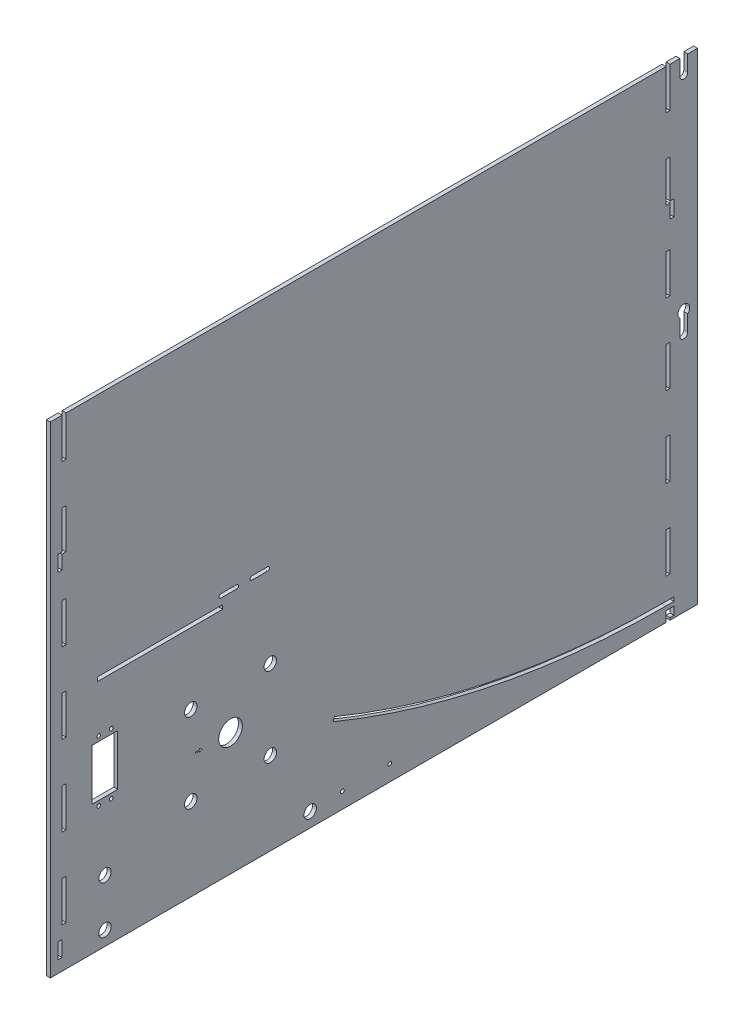
SolidWorks part; units mm, degrees
ref_plane "Front Plane" through (0, 0, 0) normal (0, 0, 1) x (1, 0, 0)
ref_plane "Top Plane" through (0, 0, 0) normal (0, 1, 0) x (1, 0, 0)
ref_plane "Right Plane" through (0, 0, 0) normal (1, 0, 0) x (0, 0, -1)
sketch "Sketch1" plane through (0, 0, 0) normal (1, 0, 0) x (0, 0, -1)
  line L0 (-141.0275, 130.552) -> (-77.0275, 130.552) construction
  line L1 (-244.475, 387.35) -> (244.475, 387.35)
  line L2 (-244.475, 387.35) -> (-244.475, 0)
  line L3 (-244.475, 0) -> (244.475, 0)
  line L4 (244.475, 387.35) -> (244.475, 0)
  line L5 (-77.0275, 130.552) -> (-77.0275, 66.552) construction
  line L6 (-77.0275, 66.552) -> (-141.0275, 66.552) construction
  line L7 (-141.0275, 66.552) -> (-141.0275, 130.552) construction
  line L8 (-215.1157, 149.1948) -> (-204.9557, 149.1948) construction
  line L9 (-220.2857, 145.2948) -> (-199.7857, 145.2948)
  line L10 (-220.2857, 145.2948) -> (-220.2857, 104.2948)
  line L11 (-220.2857, 104.2948) -> (-199.7857, 104.2948)
  line L12 (-199.7857, 145.2948) -> (-199.7857, 104.2948)
  line L15 (-204.9557, 100.3948) -> (-215.1157, 100.3948) construction
  line L18 (-210.0357, 100.3948) -> (-210.0357, 149.1948) construction
  line L19 (-220.2857, 124.7948) -> (-199.7857, 124.7948) construction
  line L20 (-241.3, 387.35) -> (-241.3, 0) construction
  line L21 (241.3, 387.35) -> (241.3, 0) construction
  line L22 (-244.475, 193.675) -> (-241.3, 193.675) construction
  line L23 (244.475, 193.675) -> (241.3, 193.675) construction
  line L24 (-244.475, 6.35) -> (244.475, 6.35) construction
  line L25 (-241.3, 190.754) -> (-215.9, 190.754) construction
  line L26 (-115.3775, 190.754) -> (-109.0275, 190.754) construction
  line L27 (-215.9, 190.754) -> (-115.3775, 190.754)
  line L28 (-215.9, 190.754) -> (-215.9, 187.579)
  line L29 (-215.9, 187.579) -> (-115.3775, 187.579)
  line L30 (-115.3775, 190.754) -> (-115.3775, 187.579)
  line L31 (-109.0275, 190.754) -> (-109.0275, 187.579) construction
  line L32 (-109.0275, 187.579) -> (-115.3775, 187.579) construction
  line L33 (-215.9, 187.579) -> (-241.3, 187.579) construction
  line L34 (-26.6311, 64.8518) -> (-25.4161, 67.7851)
  line L35 (241.3, 11.557) -> (241.3, 14.732)
  line L36 (-26.0236, 66.3185) -> (-68.1062, 83.7497) construction
  line L37 (241.3, 13.1445) -> (249.9158, 13.1445) construction
  line L38 (-26.0236, 66.3185) -> (-57.3534, 66.3185) construction
  line L39 (-91.8775, 197.579) -> (-116.8775, 197.579) construction
  line L40 (-244.475, 387.35) -> (-254, 387.35)
  line L41 (-244.475, 387.35) -> (-244.475, 0)
  line L42 (-244.475, 0) -> (-254, 0)
  line L43 (-254, 387.35) -> (-254, 0)
  line L44 (244.475, 387.35) -> (266.7, 387.35)
  line L45 (244.475, 387.35) -> (244.475, 0)
  line L46 (244.475, 0) -> (266.7, 0)
  line L47 (266.7, 387.35) -> (266.7, 0)
  line L48 (-116.8775, 199.079) -> (-104.1775, 199.079)
  line L49 (-104.1775, 196.079) -> (-116.8775, 196.079)
  line L50 (-91.8775, 196.079) -> (-79.1775, 196.079)
  line L51 (-79.1775, 199.079) -> (-91.8775, 199.079)
  circle A0 centre (-109.0275, 98.552) radius 89.027 construction
  circle A1 centre (-109.0275, 98.552) radius 9.525
  circle A2 centre (-141.0275, 130.552) radius 5
  circle A3 centre (-77.0275, 130.552) radius 5
  circle A4 centre (-141.0275, 66.552) radius 5
  circle A5 centre (-77.0275, 66.552) radius 5
  circle A10 centre (-215.1157, 149.1948) radius 1.5
  circle A11 centre (-204.9557, 149.1948) radius 1.5
  circle A12 centre (-215.1157, 100.3948) radius 1.5
  circle A13 centre (-204.9557, 100.3948) radius 1.5
  arc A14 (241.3, 11.557) -> (-26.6311, 64.8518) centre (241.3, 711.6946) cw
  arc A15 (241.3, 14.732) -> (-25.4161, 67.7851) centre (241.3, 711.6946) cw
  arc A16 (241.3, 13.1445) -> (-26.0236, 66.3185) centre (241.3, 711.6946) cw construction
  circle A17 centre (-116.8775, 197.579) radius 1.5
  circle A18 centre (-91.8775, 197.579) radius 1.5
  arc A19 (-104.1775, 199.079) -> (-104.1775, 196.079) centre (-104.1775, 197.579) cw
  arc A20 (-79.1775, 196.079) -> (-79.1775, 199.079) centre (-79.1775, 197.579) ccw
  point P16 (-109.0275, 130.552)
  point P18 (-141.0275, 98.552)
  point P31 (-210.0357, 104.2948)
  point P34 (-210.0357, 124.7948)
  point P38 (-198.0545, 98.552)
  point P57 (0, 0)
  point P60 (-109.0275, 9.525)
  dimension "D3" = 178.054
  dimension "D5" = 10
  dimension "D6" = 19.05
  dimension "D8" = 3
  dimension "D28" = 3
  dimension "D4" = 64
  dimension "D7" = 10.16
  dimension "D9" = 20.5
  dimension "D10" = 41
  dimension "D11" = 48.8
  dimension "D12" = 11.9812
  dimension "D13" = 26.2428
  dimension "D14" = 3.175
  dimension "D15" = 482.6
  dimension "D16" = 6.35
  dimension "D2" = 381
  dimension "D17" = 25.4
  dimension "D18" = 3.175
  dimension "D19" = 6.35
  dimension "D20" = 100.5225
  dimension "D21" = 9.525
  dimension "D23" = 3.175
  dimension "D24" = 13.1445
  dimension "D25" = 22.5
  dimension "D26" = 9.525
  dimension "D27" = 22.225
  dimension "D29" = 6.825
  dimension "D30" = 25
  dimension "D31" = 12.7
  dimension "D32" = 1.5
  dimension "D22" = 274.32
extrude "Boss-Extrude1" add sketch "Sketch1" along normal blind 3.175 contours L4 L1 L2 L3 A15 L35 A14 L34 A13 A12 A11 A10 A5 A4 A3 A2 A1 L9 L12 L11 L10 L27 L30 L29 L28 | L47 L44 L4 L46 | L40 L43 L42 L2 region at (0, 195.0661, -1.1642) region at (0, 193.675, 249.2375) region at (0, 193.675, -255.5875)
sketch "Sketch2" plane through (0, 0, 0) normal (-1, 0, 0) x (0, 0, 1)
  line L34 (-241.3, 387.35) -> (-241.3, 0) construction
  line L35 (-244.475, 387.35) -> (-241.3, 387.35)
  line L36 (-244.475, 387.35) -> (-244.475, 355.0708)
  line L37 (-244.475, 355.0708) -> (-241.3, 355.0708)
  line L38 (-241.3, 387.35) -> (-241.3, 355.0708)
  line L39 (241.3, 387.35) -> (241.3, 0) construction
  line L40 (244.475, 387.35) -> (241.3, 387.35)
  line L41 (244.475, 387.35) -> (244.475, 355.0708)
  line L42 (244.475, 355.0708) -> (241.3, 355.0708)
  line L43 (241.3, 387.35) -> (241.3, 355.0708)
  line L44 (-244.475, 355.0708) -> (-244.475, 322.7917)
  line L45 (-244.475, 355.0708) -> (-241.3, 355.0708)
  line L46 (-241.3, 355.0708) -> (-241.3, 322.7917)
  line L47 (-244.475, 322.7917) -> (-241.3, 322.7917)
  line L48 (244.475, 355.0708) -> (244.475, 322.7917)
  line L49 (244.475, 355.0708) -> (241.3, 355.0708)
  line L50 (241.3, 355.0708) -> (241.3, 322.7917)
  line L51 (244.475, 322.7917) -> (241.3, 322.7917)
  line L52 (-244.475, 322.7917) -> (-244.475, 290.5125)
  line L53 (-244.475, 322.7917) -> (-241.3, 322.7917)
  line L54 (-241.3, 322.7917) -> (-241.3, 290.5125)
  line L55 (-244.475, 290.5125) -> (-241.3, 290.5125)
  line L56 (244.475, 322.7917) -> (244.475, 290.5125)
  line L57 (244.475, 322.7917) -> (241.3, 322.7917)
  line L58 (241.3, 322.7917) -> (241.3, 290.5125)
  line L59 (244.475, 290.5125) -> (241.3, 290.5125)
  line L60 (-244.475, 290.5125) -> (-244.475, 258.2333)
  line L61 (-244.475, 290.5125) -> (-241.3, 290.5125)
  line L62 (-241.3, 290.5125) -> (-241.3, 258.2333)
  line L63 (-244.475, 258.2333) -> (-241.3, 258.2333)
  line L64 (244.475, 290.5125) -> (244.475, 258.2333)
  line L65 (244.475, 290.5125) -> (241.3, 290.5125)
  line L66 (241.3, 290.5125) -> (241.3, 258.2333)
  line L67 (244.475, 258.2333) -> (241.3, 258.2333)
  line L68 (-244.475, 258.2333) -> (-244.475, 225.9542)
  line L69 (-244.475, 258.2333) -> (-241.3, 258.2333)
  line L70 (-241.3, 258.2333) -> (-241.3, 225.9542)
  line L71 (-244.475, 225.9542) -> (-241.3, 225.9542)
  line L72 (244.475, 258.2333) -> (244.475, 225.9542)
  line L73 (244.475, 258.2333) -> (241.3, 258.2333)
  line L74 (241.3, 258.2333) -> (241.3, 225.9542)
  line L75 (244.475, 225.9542) -> (241.3, 225.9542)
  line L76 (-244.475, 225.9542) -> (-244.475, 193.675)
  line L77 (-244.475, 225.9542) -> (-241.3, 225.9542)
  line L78 (-241.3, 225.9542) -> (-241.3, 193.675)
  line L79 (-244.475, 193.675) -> (-241.3, 193.675)
  line L80 (244.475, 225.9542) -> (244.475, 193.675)
  line L81 (244.475, 225.9542) -> (241.3, 225.9542)
  line L82 (241.3, 225.9542) -> (241.3, 193.675)
  line L83 (244.475, 193.675) -> (241.3, 193.675)
  line L84 (-244.475, 193.675) -> (-244.475, 161.3958)
  line L85 (-244.475, 193.675) -> (-241.3, 193.675)
  line L86 (-241.3, 193.675) -> (-241.3, 161.3958)
  line L87 (-244.475, 161.3958) -> (-241.3, 161.3958)
  line L88 (244.475, 193.675) -> (244.475, 161.3958)
  line L89 (244.475, 193.675) -> (241.3, 193.675)
  line L90 (241.3, 193.675) -> (241.3, 161.3958)
  line L91 (244.475, 161.3958) -> (241.3, 161.3958)
  line L92 (-244.475, 161.3958) -> (-244.475, 129.1167)
  line L93 (-244.475, 161.3958) -> (-241.3, 161.3958)
  line L94 (-241.3, 161.3958) -> (-241.3, 129.1167)
  line L95 (-244.475, 129.1167) -> (-241.3, 129.1167)
  line L96 (244.475, 161.3958) -> (244.475, 129.1167)
  line L97 (244.475, 161.3958) -> (241.3, 161.3958)
  line L98 (241.3, 161.3958) -> (241.3, 129.1167)
  line L99 (244.475, 129.1167) -> (241.3, 129.1167)
  line L100 (-244.475, 129.1167) -> (-244.475, 96.8375)
  line L101 (-244.475, 129.1167) -> (-241.3, 129.1167)
  line L102 (-241.3, 129.1167) -> (-241.3, 96.8375)
  line L103 (-244.475, 96.8375) -> (-241.3, 96.8375)
  line L104 (244.475, 129.1167) -> (244.475, 96.8375)
  line L105 (244.475, 129.1167) -> (241.3, 129.1167)
  line L106 (241.3, 129.1167) -> (241.3, 96.8375)
  line L107 (244.475, 96.8375) -> (241.3, 96.8375)
  line L108 (0, 387.35) -> (0, 0) construction
  line L109 (244.475, 387.35) -> (-244.475, 387.35) construction
  line L110 (-244.475, 96.8375) -> (-244.475, 64.5583)
  line L111 (-244.475, 96.8375) -> (-241.3, 96.8375)
  line L112 (-241.3, 96.8375) -> (-241.3, 64.5583)
  line L113 (-244.475, 64.5583) -> (-241.3, 64.5583)
  line L114 (244.475, 96.8375) -> (244.475, 64.5583)
  line L115 (244.475, 96.8375) -> (241.3, 96.8375)
  line L116 (241.3, 96.8375) -> (241.3, 64.5583)
  line L117 (244.475, 64.5583) -> (241.3, 64.5583)
  line L118 (-244.475, 64.5583) -> (-244.475, 32.2792)
  line L119 (-244.475, 64.5583) -> (-241.3, 64.5583)
  line L120 (-241.3, 64.5583) -> (-241.3, 32.2792)
  line L121 (-244.475, 32.2792) -> (-241.3, 32.2792)
  line L122 (244.475, 64.5583) -> (244.475, 32.2792)
  line L123 (244.475, 64.5583) -> (241.3, 64.5583)
  line L124 (241.3, 64.5583) -> (241.3, 32.2792)
  line L125 (244.475, 32.2792) -> (241.3, 32.2792)
  line L126 (-244.475, 32.2792) -> (-244.475, 0)
  line L127 (-244.475, 32.2792) -> (-241.3, 32.2792)
  line L128 (-241.3, 32.2792) -> (-241.3, 0)
  line L129 (-244.475, 0) -> (-241.3, 0)
  line L130 (244.475, 32.2792) -> (244.475, 0)
  line L131 (244.475, 32.2792) -> (241.3, 32.2792)
  line L132 (241.3, 32.2792) -> (241.3, 0)
  line L133 (244.475, 0) -> (241.3, 0)
  line M136 (254, 387.35) -> (-266.7, 387.35)
  dimension "D2" = 387.35
  dimension "D3" = 32.2792
  dimension "D1" = 12
extrude "Cut-Extrude1" cut sketch "Sketch2" against normal through all contours L118 L121 L120 L113 | L100 L103 L102 L95 | L84 L87 L86 L79 | L52 L55 L54 L47 | L38 L36 L37 M136 | L68 L71 L70 L63 | L43 L42 L41 M136 | L59 L56 L51 L58 | L75 L72 L67 L74 | L91 L88 L83 L90 | L107 L104 L99 L106 | L125 L122 L117 L124 region at (0, 371.2104, 242.8875) region at (0, 371.2104, -242.8875) region at (0, 306.6521, -242.8875) region at (0, 306.6521, 242.8875) region at (0, 242.0938, -242.8875) region at (0, 242.0938, 242.8875) region at (0, 177.5354, -242.8875) region at (0, 177.5354, 242.8875) region at (0, 112.9771, -242.8875) region at (0, 112.9771, 242.8875) region at (0, 48.4188, -242.8875) region at (0, 48.4188, 242.8875)
sketch "Sketch3" plane through (0, 0, 0) normal (-1, 0, 0) x (0, 0, 1)
  line L0 (-258.7625, 206.375) -> (-258.7625, 193.675)
  line L1 (-252.4125, 193.675) -> (-252.4125, 206.375)
  line L2 (-258.7625, 387.35) -> (-258.7625, 374.65)
  line L3 (-244.475, 387.35) -> (-266.7, 387.35) construction
  line L4 (-252.4125, 374.65) -> (-252.4125, 387.35)
  line L5 (-258.7625, 387.35) -> (-252.4125, 387.35)
  line L6 (-255.5875, 374.65) -> (-255.5875, 193.675) construction
  line L7 (-266.7, 387.35) -> (-266.7, 0) construction
  line L9 (-241.3, 11.557) -> (-247.65, 11.557)
  line L10 (-241.3, 11.557) -> (-241.3, 14.732)
  line L11 (-241.3, 14.732) -> (-247.65, 14.732)
  line L12 (-247.65, 11.557) -> (-247.65, 14.732)
  circle A0 centre (-255.5875, 209.9248) radius 4.7625
  arc A1 (-258.7625, 193.675) -> (-252.4125, 193.675) centre (-255.5875, 193.675) ccw
  arc A2 (-258.7625, 374.65) -> (-252.4125, 374.65) centre (-255.5875, 374.65) ccw
  point P16 (-255.5875, 387.35)
  point P17 (-255.5875, 387.35)
  point P24 (-266.7, 193.675)
  dimension "D1" = 3.175
  dimension "D2" = 9.525
  dimension "D3" = 12.7
  dimension "D4" = 6.35
extrude "Cut-Extrude2" cut sketch "Sketch3" against normal through all contours L12 L9 L10 L11 | A0 L6 | L0 A1 L1 A0 | L6 A0 | L2 A2 L4 L5 region at (0, 205.316, -257.3479) region at (0, 379.7367, -255.5875) region at (0, 209.9248, -257.6088) region at (0, 209.9248, -253.5662) region at (0, 13.1445, -244.475)
sketch "Sketch4" plane through (0, 0, 0) normal (-1, 0, 0) x (0, 0, 1)
  line L0 (210.0357, 49.5948) -> (210.0357, 11.4948) construction
  line L1 (210.0357, 11.4948) -> (44.9357, 11.4948) construction
  line L2 (210.0357, 49.5948) -> (210.0357, 100.3948) construction
  circle A0 centre (210.0357, 49.5948) radius 5
  circle A1 centre (44.9357, 11.4948) radius 5
  circle A2 centre (210.0357, 11.4948) radius 5
  dimension "D1" = 10
  dimension "D2" = 50.8
  dimension "D3" = 38.1
  dimension "D4" = 165.1
extrude "Cut-Extrude3" cut sketch "Sketch4" against normal through all
sketch "Sketch5" plane through (0, 0, 0) normal (-1, 0, 0) x (0, 0, 1)
  line L0 (244.475, 0) -> (-244.475, 0) construction
  line L1 (-19.05, 12.7) -> (19.05, 12.7) construction
  circle A0 centre (-19.05, 12.7) radius 1.5
  circle A1 centre (19.05, 12.7) radius 1.5
  point P6 (0, 12.7)
  dimension "D3" = 3
  dimension "D1" = 38.1
  dimension "D2" = 12.7
extrude "Cut-Extrude4" cut sketch "Sketch5" against normal through all
sketch "Sketch6" plane through (0, 0, 0) normal (-1, 0, 0) x (0, 0, 1)
  line L0 (244.475, 387.35) -> (244.475, 355.0708) construction
  line L1 (244.475, 292.1) -> (247.65, 292.1)
  line L2 (244.475, 292.1) -> (244.475, 279.4)
  line L3 (244.475, 279.4) -> (247.65, 279.4)
  line L4 (247.65, 292.1) -> (247.65, 279.4)
  line L6 (244.475, 64.5583) -> (244.475, 32.2792) construction
  line L7 (244.475, 9.525) -> (247.65, 9.525)
  line L8 (244.475, 9.525) -> (244.475, 22.225)
  line L9 (244.475, 22.225) -> (247.65, 22.225)
  line L10 (247.65, 9.525) -> (247.65, 22.225)
  line L11 (-244.475, 322.7917) -> (-244.475, 290.5125) construction
  line L12 (-247.65, 279.4) -> (-244.475, 279.4)
  line L13 (-247.65, 279.4) -> (-247.65, 292.1)
  line L14 (-247.65, 292.1) -> (-244.475, 292.1)
  line L15 (-244.475, 279.4) -> (-244.475, 292.1)
  line L16 (-244.475, 64.5583) -> (-244.475, 32.2792) construction
  line L17 (-244.475, 1.905) -> (-247.65, 1.905)
  line L18 (-244.475, 1.905) -> (-244.475, 8.255)
  line L19 (-244.475, 8.255) -> (-247.65, 8.255)
  line L20 (-247.65, 1.905) -> (-247.65, 8.255)
  line L21 (254, 387.35) -> (244.475, 387.35) construction
  line L22 (-241.3, 8.255) -> (-238.125, 8.255)
  line L23 (-241.3, 8.255) -> (-241.3, 1.905)
  line L24 (254, 0) -> (-266.7, 0) construction
  line L25 (-241.3, 1.905) -> (-238.125, 1.905)
  line L26 (-244.475, 8.255) -> (-241.3, 8.255)
  line L27 (-244.475, 8.255) -> (-244.475, 0)
  line L28 (-244.475, 0) -> (-241.3, 0)
  line L29 (-241.3, 8.255) -> (-241.3, 0)
  line L30 (-238.125, 8.255) -> (-238.125, 1.905)
  circle A0 centre (-247.65, 5.08) radius 1.5 construction
  point P28 (244.475, 285.75)
  dimension "D4" = 3
  dimension "D2" = 3.175
  dimension "D3" = 12.7
  dimension "D5" = 6.35
  dimension "D6" = 3.175
  dimension "D7" = 8.255
  dimension "D8" = 9.525
  dimension "D1" = 101.6
extrude "Cut-Extrude5" cut sketch "Sketch6" against normal through all contours L29 L26 L18 L27 L28 | L12 L15 L14 L13 | L4 L1 L2 L3 | L7 L10 L9 L8 | L20 L17 L18 L19 region at (0, 285.75, 246.0625) region at (0, 15.875, 246.0625) region at (0, 285.75, -246.0625) region at (0, 5.08, -246.0625) region at (0, 4.1275, -242.8875)
sketch "Sketch7" plane through (0, 0, 0) normal (-1, 0, 0) x (0, 0, 1)
  line L0 (118.5525, 98.552) -> (137.1247, 98.552) construction
  line L1 (137.1247, 98.9489) -> (137.1247, 98.1551)
  line L2 (137.1247, 98.1551) -> (133.9497, 98.1551)
  line L7 (133.9497, 98.9489) -> (137.1247, 98.9489)
  line L17 (131.8875, 98.5393) -> (131.8875, 98.5647) construction
  line L20 (133.9497, 98.9489) -> (133.9497, 99.7426)
  line L21 (133.9497, 99.7426) -> (131.8875, 98.552)
  line L22 (131.8875, 98.552) -> (133.9497, 97.3614)
  line L23 (133.9497, 97.3614) -> (133.9497, 98.1551)
  circle A0 centre (109.0275, 98.552) radius 9.525 construction
  point P14 (137.1247, 98.552)
  point P18 (131.8875, 98.552)
  dimension "D1" = 0.7937
  dimension "D2" = 30
  dimension "D3" = 13.335
  dimension "D4" = 3.175
  dimension "D5" = 0.0254
  dimension "D6" = 0.7937
extrude "Cut-Extrude6" cut sketch "Sketch7" against normal through all contours L7 L2 L1 | L7 | L2 | L2 | L7 region at (0, 98.552, 134.4146)
equation "\"wallThickness\"= .125in"
equation "\"bottomThickness\"= .25"
equation "\"D14@Sketch1\"=\"wallThickness\""
equation "\"D16@Sketch1\"=\"bottomThickness\""
equation "\"D18@Sketch1\"=\"wallThickness\""
equation "\"D23@Sketch1\"=\"wallThickness\""
equation "\"D1@Boss-Extrude1\"=\"wallThickness\""
equation "\"D3@Sketch2\"=\"D2@Sketch2\" / \"D1@Sketch2\""
equation "\"chamberHeight\"= 15"
equation "\"D2@Sketch1\"=\"chamberHeight\""
equation "\"D6@Sketch6\"=\"wallThickness\""
